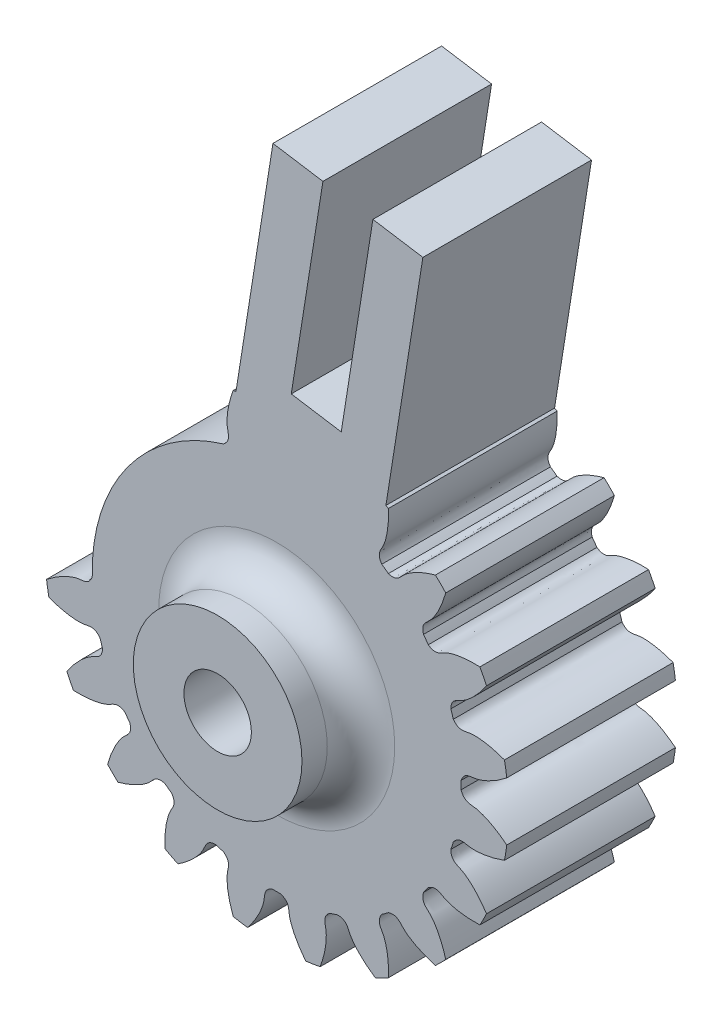
SolidWorks part; units mm, degrees
note: '?' marks a value the reader was unsure of.
material "聚脂树脂"
ref_plane "前视基准面" through (0, 0, 0) normal (0, 0, 1) x (1, 0, 0)
ref_plane "上视基准面" through (0, 0, 0) normal (0, 1, 0) x (1, 0, 0)
ref_plane "右视基准面" through (0, 0, 0) normal (1, 0, 0) x (0, 0, -1)
other "Configuration Table"
sketch "草图1" plane through (0, 0, 0) normal (0, 0, 1) x (1, 0, 0)
  circle A0 centre (0, 0) radius 13.75
extrude "凸台-拉伸1" add sketch "草图1" along normal blind 10
ref_axis "基准轴1" through (0, 0, -1.5) along (0, 0, 1)?
sketch "草图2" plane through (0, 0, 0) normal (0, 0, 1) x (1, 0, 0)
  line L0 (0, 0) -> (0, 13.75) construction
  circle A0 centre (0, 0) radius 13.75 construction
  arc A1 (0.2416, 10.9348) -> (-0.2416, 10.9348) centre (0, 0) ccw
  arc A2 (3.9764, 15.6228) -> (-3.9764, 15.6228) centre (0, 0) ccw
  spline S0 degree 3 poles (0.2416, 10.9348) (0.764, 11.1168) (0.6964, 11.4839) (0.7661, 11.8375) (0.7736, 11.8719) (0.7829, 11.9108) (0.7941, 11.954) (0.8075, 12.0015) (0.8231, 12.0532) (0.8413, 12.1091) (0.8621, 12.169) (0.8857, 12.2329) (0.9123, 12.3007) (0.9421, 12.3723) (0.9752, 12.4476) (1.0117, 12.5264) (1.0519, 12.6088) (1.0959, 12.6945) (1.1438, 12.7834) (1.1957, 12.8755) (1.2519, 12.9705) (1.3125, 13.0684) (1.3775, 13.1691) (1.4472, 13.2723) (1.5216, 13.3779) (1.601, 13.4858) (1.6853, 13.5958) (1.7747, 13.7078) (1.8694, 13.8216) (1.9693, 13.937) (2.0748, 14.0539) (2.1857, 14.1721) (2.3023, 14.2914) (2.4246, 14.4116) (2.5527, 14.5326) (2.6866, 14.6542) (2.8265, 14.7761) (2.9725, 14.8983) (3.1245, 15.0204) (3.2826, 15.1424) (3.4469, 15.2639) (3.6768, 15.427) (3.8549, 15.5454) (3.9764, 15.6228) knots 0 0 0 0 0.165916 0.170906 0.176664 0.183189 0.190482 0.198542 0.207371 0.216967 0.22733 0.238462 0.250361 0.263027 0.276462 0.290664 0.305634 0.321371 0.337876 0.355149 0.37319 0.391998 0.411574 0.431917 0.453028 0.474907 0.497554 0.520968 0.54515 0.570099 0.595817 0.622302 0.649554 0.677575 0.706363 0.735918 0.766242 0.797333 0.829191 0.861818 0.895212 0.929373 1 1 1 1
  spline S1 degree 3 poles (-0.2416, 10.9348) (-0.764, 11.1168) (-0.6964, 11.4839) (-0.7661, 11.8375) (-0.7736, 11.8719) (-0.7829, 11.9108) (-0.7941, 11.954) (-0.8075, 12.0015) (-0.8231, 12.0532) (-0.8413, 12.1091) (-0.8621, 12.169) (-0.8857, 12.2329) (-0.9123, 12.3007) (-0.9421, 12.3723) (-0.9752, 12.4476) (-1.0117, 12.5264) (-1.0519, 12.6088) (-1.0959, 12.6945) (-1.1438, 12.7834) (-1.1957, 12.8755) (-1.2519, 12.9705) (-1.3125, 13.0684) (-1.3775, 13.1691) (-1.4472, 13.2723) (-1.5216, 13.3779) (-1.601, 13.4858) (-1.6853, 13.5958) (-1.7747, 13.7078) (-1.8694, 13.8216) (-1.9693, 13.937) (-2.0748, 14.0539) (-2.1857, 14.1721) (-2.3023, 14.2914) (-2.4246, 14.4116) (-2.5527, 14.5326) (-2.6866, 14.6542) (-2.8265, 14.7761) (-2.9725, 14.8983) (-3.1245, 15.0204) (-3.2826, 15.1424) (-3.4469, 15.2639) (-3.6768, 15.427) (-3.8549, 15.5454) (-3.9764, 15.6228) knots 0 0 0 0 0.165916 0.170906 0.176664 0.183189 0.190482 0.198542 0.207371 0.216967 0.22733 0.238462 0.250361 0.263027 0.276462 0.290664 0.305634 0.321371 0.337876 0.355149 0.37319 0.391998 0.411574 0.431917 0.453028 0.474907 0.497554 0.520968 0.54515 0.570099 0.595817 0.622302 0.649554 0.677575 0.706363 0.735918 0.766242 0.797333 0.829191 0.861818 0.895212 0.929373 1 1 1 1
extrude "切除-拉伸1" cut sketch "草图2" along normal through all
pattern_circular "阵列(圆周)1" count 20 every 18 about axis through (0, 0, -1.5) along (0, 0, 1) of "切除-拉伸1"
sketch "草图3" plane through (0, 0, 0) normal (0, 0, 1) x (1, 0, 0)
  circle A0 centre (0, 0) radius 12.5 construction
  dimension "Dn" = 25
sketch "草图6" plane through (0, 0, 0) normal (0, 0, -1) x (-1, 0, 0)
  line L0 (0, 0) -> (-10.311, 65.1009) construction
  line L1 (0, 0) -> (38.9643, 6.1713) construction
  line L2 (0, 0) -> (-30.4582, -4.8241) construction
  line L3 (-12.3461, -1.9554) -> (-21.1812, 53.827) construction
  line L4 (4.4446, 0.704) -> (-1.1233, 35.8583)
  line L5 (-4.4446, -0.704) -> (-10.0125, 34.4504)
  line L6 (-10.0125, 34.4504) -> (-15.7198, 70.4851)
  line L7 (-15.7198, 70.4851) -> (-21.4537, 55.5478) construction
  line L8 (-15.7198, 70.4851) -> (-7.9754, 90.6601) construction
  line L9 (-15.7198, 70.4851) -> (-11.3112, 81.9699)
  line L10 (-4.4446, -0.704) -> (4.4446, 0.704)
  circle A0 centre (0, 0) radius 12.5 construction
  circle A1 centre (-21.4537, 55.5478) radius 24 construction
  circle A2 centre (-21.4537, 55.5478) radius 28.3019 construction
  arc A3 (-11.3112, 81.9699) -> (-1.1233, 35.8583) centre (-21.4537, 55.5478) cw
  dimension "D1" = 25
  dimension "D4" = 48
  dimension "D5" = 30
  dimension "D2" = 9
  dimension "D3" = 58.22
extrude "凸台-拉伸2" add sketch "草图6" against normal blind 15 and the other way blind 5
sketch "草图7" plane through (4.4446, -0.704, 0) normal (0.9877, -0.1564, 0) x (0, 0, -1)
  line L0 (0, 0) -> (0, 32)
  line L1 (0, 32) -> (5, 32)
  line L2 (5, 0) -> (5, 72.0764) construction
  line L3 (5, 32) -> (5, 0)
  line L4 (5, 0) -> (0, 0) construction
  line L5 (5, 0) -> (5, 72.0764) construction
  line L6 (5, 0) -> (0, 0)
  line L7 (-5, 4.6588) -> (-5, 27.3083) construction
  line L8 (-10, 4.6588) -> (0, 4.6588) construction
  line L9 (-15, 32) -> (-15, 0)
  line L10 (-10, 32) -> (-15, 32)
  line L11 (-10, 0) -> (-10, 32)
  line L12 (-15, 0) -> (-10, 0)
  dimension "D1" = 32
extrude "切除-拉伸3" cut sketch "草图7" against normal blind 32 and the other way blind 10
ref_plane "基准面1" through (12.5, 0, 0) normal (1, 0, 0) x (0, 0, -1)
ref_axis "基准轴2" through (0, 0, -6) along (0, 0, 1)?
ref_plane "基准面2" through (0, 0, 0) normal (-0.9877, 0.1564, 0) x (0, 0, 1)
ref_plane "基准面3" through (12.3461, -1.9554, 0) normal (-0.9877, 0.1564, 0) x (0, 0, 1)
sketch "草图13" plane through (12.3461, -1.9554, 0) normal (-0.9877, 0.1564, 0) x (0, 0, 1)
  line L0 (5, 0.4331) -> (5, 90.5431) construction
  line L1 (0, 0.4331) -> (10, 0.4331) construction
  line L2 (5, 82.6531) -> (5, 34.6531)
  arc A0 (5, 82.6531) -> (5, 34.6531) centre (5, 58.6531) cw
  dimension "D1" = 24
  dimension "D2" = 58.22
revolve "切除-旋转2" cut sketch "草图13" angle 360 about L0
sketch "草图12" plane through (0, 0, -5) normal (0, 0, -1) x (-1, 0, 0)
  line L0 (0, 0) -> (-14.3434, 90.5607) construction
  line L1 (-12.3461, -1.9554) -> (-26.4984, 87.3984) construction
  line L2 (-11.6703, 81.0345) -> (-11.3112, 81.9699)
  line L3 (0, 0) -> (-28.4747, -4.5099) construction
  line L4 (-1.1233, 35.8583) -> (-1.3214, 37.1092)
  line L5 (-0.5613, 32.31) -> (-1.1233, 35.8583) construction
  line L6 (-13.501, 76.2653) -> (-11.3112, 81.9699) construction
  circle A0 centre (-21.4537, 55.5478) radius 28.3019
  circle A1 centre (-21.4537, 55.5478) radius 27.3
  dimension "D3" = 54.6
  dimension "D4" = 56.6039
  dimension "D1" = 12.5
  dimension "D2" = 58.22
extrude "切除-拉伸4" cut sketch "草图12" against normal blind 22
fillet "圆角2" radius 2 4 edges at (5.0059, 31.606, 10) (5.0059, 31.606, 15) (5.0059, 31.606, 0) (5.0059, 31.606, -5)
fillet "圆角3" radius 3 2 edges at (-5.1188, 61.8083, 15) (-5.1188, 61.8083, -5)
sketch "草图16" plane through (0, 0, 10) normal (0, 0, 1) x (1, 0, 0)
  circle A0 centre (0, 0) radius 2
  dimension "D1" = 4
extrude "切除-拉伸5" cut sketch "草图16" against normal blind 16.5
sketch "草图18" plane through (0, 0, 10) normal (0, 0, 1) x (1, 0, 0)
  circle A0 centre (0, 0) radius 5
  circle A1 centre (0, 0) radius 2
  dimension "D1" = 10
  dimension "D2" = 4
extrude "凸台-拉伸4" add sketch "草图18" along normal blind 3.5
sketch "草图19" plane through (0, 0, 0) normal (0, 0, -1) x (-1, 0, 0)
  circle A0 centre (0, 0) radius 8
  dimension "D1" = 16
extrude "切除-拉伸7" cut sketch "草图19" against normal blind 3
fillet "圆角4" radius 2 1 edges at (5, 0, 10)
sketch "草图20" plane through (0, 0, 0) normal (0, 0, -1) x (-1, 0, 0)
  line L0 (0, 0) -> (3.6089, 10.325)
  line L1 (3.6089, 10.325) -> (7.1451, 20.4421)
  line L2 (0, 0) -> (10.9348, -0.2416)
  line L3 (10.9348, -0.2416) -> (20.7519, -0.2416)
  circle A0 centre (0, 0) radius 17.5
  circle A1 centre (0, 0) radius 10.9375
  arc A2 (-8.7044, 6.6228) -> (-8.9885, 6.2318) centre (0, 0) ccw construction
  dimension "D1" = 35
extrude "切除-拉伸8" cut sketch "草图20" against normal blind 10 contours A1 L3 A0 L1
sketch "草图21" plane through (0, 0, 0) normal (0, 0, -1) x (-1, 0, 0)
  line L0 (0, 0) -> (0, 79.6927) construction
  line L1 (0, 0) -> (-12.0171, 75.8728) construction
  line L2 (0, 0) -> (62.9966, 9.9777) construction
  line L3 (-3.828, 14.5807) -> (-0.865, 15.05)
  line L4 (-0.865, 15.05) -> (-2.7422, 26.9022)
  line L5 (-2.7422, 26.9022) -> (17.0116, 30.0309)
  line L6 (17.0116, 30.0309) -> (7.8021, 88.1775)
  line L7 (7.8021, 88.1775) -> (-13.4539, 84.8109)
  line L8 (0, 0) -> (-24.6264, 75.7922) construction
  line L9 (-34.6685, 81.4508) -> (-13.4539, 84.8109)
  line L10 (-25.459, 23.3042) -> (-34.6685, 81.4508)
  line L11 (-5.7053, 26.4329) -> (-25.459, 23.3042)
  line L12 (-3.828, 14.5807) -> (-5.7053, 26.4329)
  point P5 (-13.3528, 84.7862)
  point P17 (-2.3465, 14.8153)
  dimension "D1" = 9
  dimension "D2" = 12
  dimension "D3" = 1.5
  dimension "D4" = 15
  dimension "D5" = 20
  dimension "D6" = 58.8714
extrude "切除-拉伸9" cut sketch "草图21" against normal blind 22 and the other way blind 36
